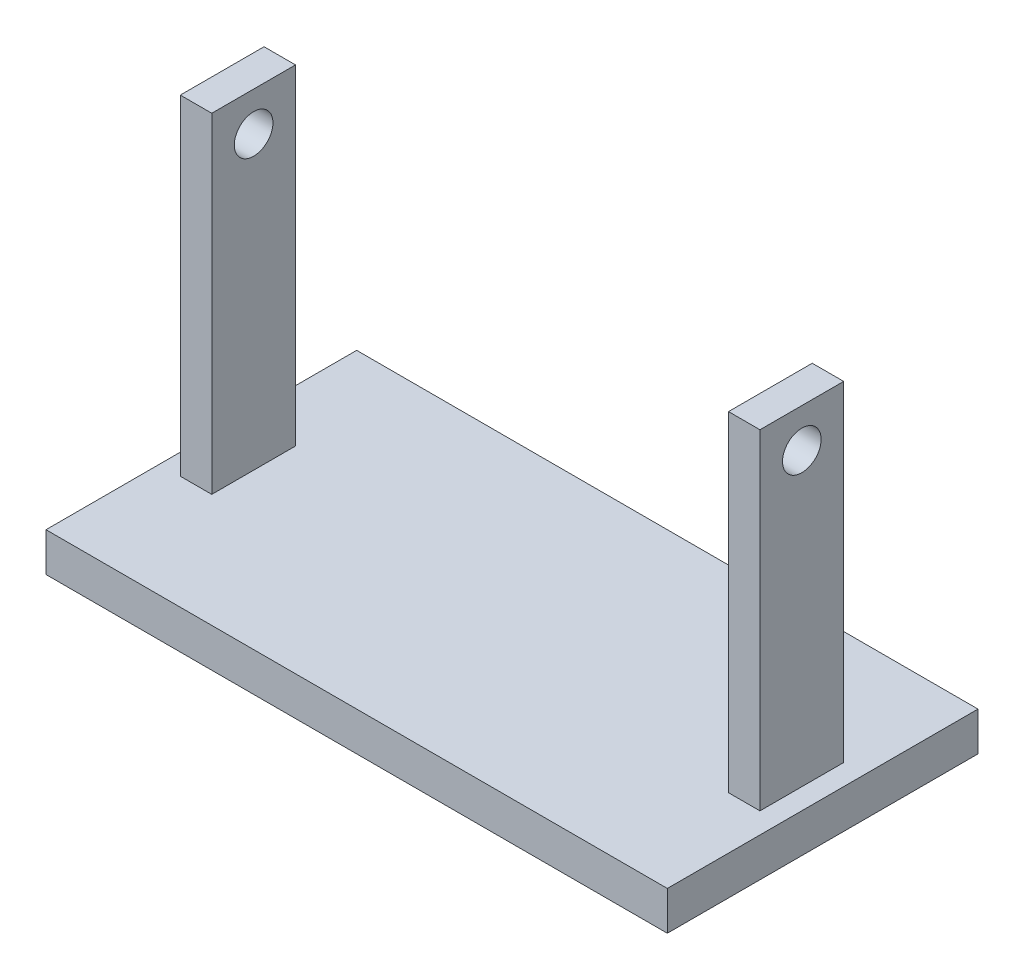
SolidWorks part; units mm, degrees
ref_plane "Front Plane" through (0, 0, 0) normal (0, 0, 1) x (1, 0, 0)
ref_plane "Top Plane" through (0, 0, 0) normal (0, 1, 0) x (1, 0, 0)
ref_plane "Right Plane" through (0, 0, 0) normal (1, 0, 0) x (0, 0, -1)
sketch "Sketch1" plane through (0, 0, 0) normal (0, 1, 0) x (1, 0, 0)
  line L0 (-80, 40) -> (-80, -40)
  line L1 (-80, 40) -> (80, 40)
  line L2 (-80, -40) -> (80, -40)
  line L3 (80, 40) -> (80, -40)
  line L4 (-80, 40) -> (80, -40) construction
  line L5 (-80, -40) -> (80, 40) construction
  line L6 (-115.6187, 0) -> (115.6187, 0) construction
  line L7 (0, 66.3406) -> (0, -66.3406) construction
  line L8 (-74.6314, 10.782) -> (-74.6314, -10.782)
  line L9 (-74.6314, 10.782) -> (-66.5327, 10.782)
  line L10 (-74.6314, -10.782) -> (-66.5327, -10.782)
  line L11 (-66.5327, 10.782) -> (-66.5327, -10.782)
  line L12 (-74.6314, 10.782) -> (-66.5327, -10.782) construction
  line L13 (-74.6314, -10.782) -> (-66.5327, 10.782) construction
  line L14 (74.6314, -10.782) -> (66.5327, -10.782)
  line L15 (66.5327, 10.782) -> (66.5327, -10.782)
  line L16 (74.6314, 10.782) -> (66.5327, 10.782)
  line L17 (74.6314, 10.782) -> (74.6314, -10.782)
  line L18 (74.6314, -10.782) -> (66.5327, 10.782) construction
  line L19 (74.6314, 10.782) -> (66.5327, -10.782) construction
  point P1 (0, 0)
  point P9 (0, 0)
  point P12 (0, 0)
  point P13 (-70.5821, 0)
  point P21 (70.5821, 0)
extrude "Boss-Extrude2" add sketch "Sketch1" along normal blind 95 contours L16 L15 L14 L17 | L9 L11 L10 L8
extrude "Boss-Extrude3" add sketch "Sketch1<5>" along normal blind 10
sketch "Sketch1<5>" plane through (0, 0, 0) normal (0, 1, 0) x (1, 0, 0) same geometry as "Sketch1"
sketch "Sketch3" plane through (74.6314, 0, 0) normal (1, 0, 0) x (0, 0, -1)
  line L0 (0, 174.5416) -> (0, -14.5416) construction
  line L2 (-10.782, 10) -> (10.782, 10) construction
  circle A0 centre (0, 85) radius 4.9732
  point P3 (0, 80)
  dimension "D1" = 75
extrude "Cut-Extrude1" cut sketch "Sketch3" against normal through all
